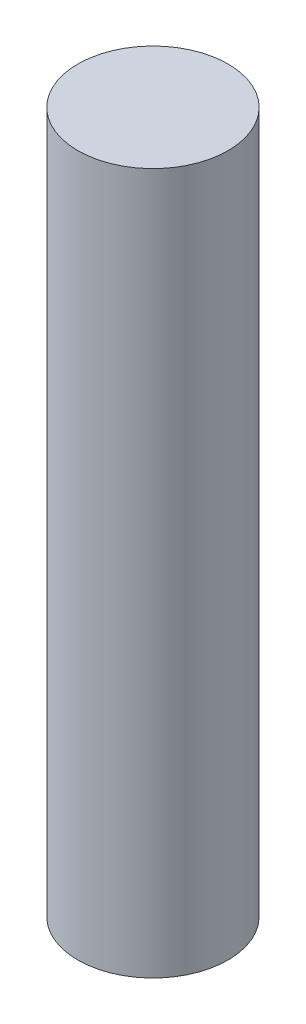
SolidWorks part; units mm, degrees
ref_plane "Front Plane" through (0, 0, 0) normal (0, 0, 1) x (1, 0, 0)
ref_plane "Top Plane" through (0, 0, 0) normal (0, 1, 0) x (1, 0, 0)
ref_plane "Right Plane" through (0, 0, 0) normal (1, 0, 0) x (0, 0, -1)
sketch "Sketch1" plane through (0, 0, 0) normal (0, 1, 0) x (1, 0, 0)
  circle A0 centre (0, 0) radius 15
  dimension "D1" = 30
extrude "Boss-Extrude1" add sketch "Sketch1" along normal blind 140
